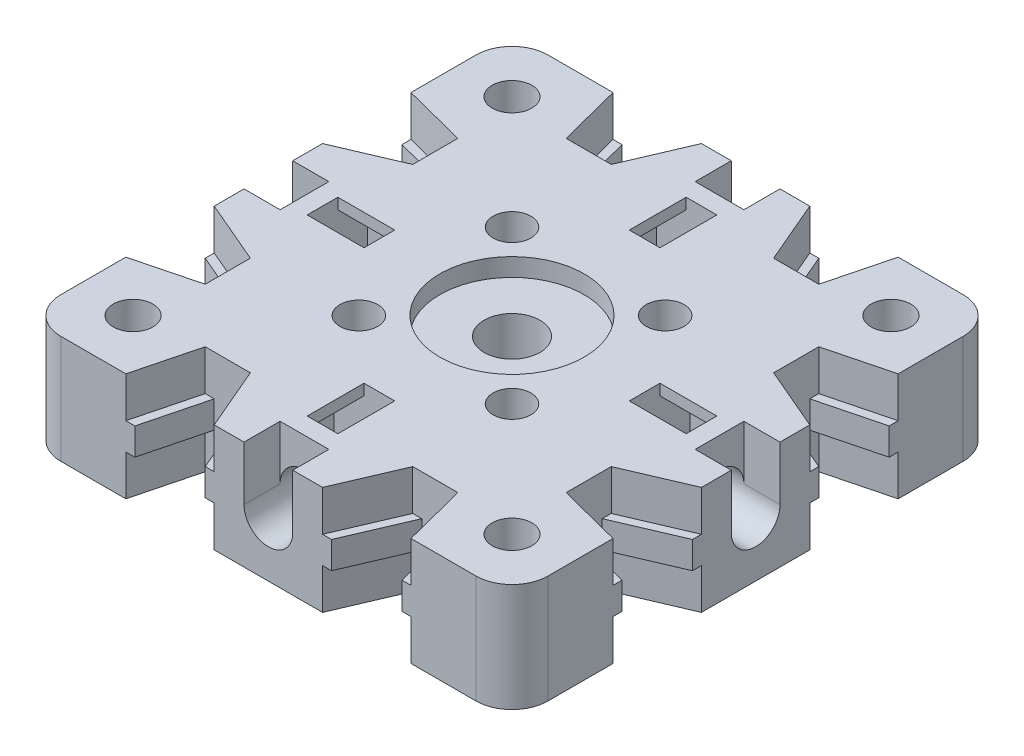
SolidWorks part; units mm, degrees
material "ABS"
ref_plane "正面" through (0, 0, 0) normal (0, 0, 1) x (1, 0, 0)
ref_plane "平面" through (0, 0, 0) normal (0, 1, 0) x (1, 0, 0)
ref_plane "右側面" through (0, 0, 0) normal (1, 0, 0) x (0, 0, -1)
sketch "ｽｹｯﾁ3" plane through (0, 0, 0) normal (0, 1, 0) x (1, 0, 0)
  line L1 (-13.5, 13.5) -> (13.5, 13.5)
  line L2 (-13.5, 13.5) -> (-13.5, -13.5)
  line L3 (-13.5, -13.5) -> (13.5, -13.5)
  line L4 (13.5, 13.5) -> (13.5, -13.5)
  line L5 (-13.5, 13.5) -> (13.5, -13.5) construction
  line L6 (-13.5, -13.5) -> (13.5, 13.5) construction
  point P0 (0, 0)
  dimension "D1" = 27
extrude "ﾎﾞｽ - 押し出し1" add sketch "ｽｹｯﾁ3" along normal mid plane 6
fillet "ﾌｨﾚｯﾄ1" radius 2 4 edges at (-13.5, 0, -13.5) (13.5, 0, -13.5) (-13.5, 0, 13.5) (13.5, 0, 13.5)
sketch "ｽｹｯﾁ4" plane through (0, 3, 0) normal (0, 1, 0) x (1, 0, 0)
  line L1 (-10.5, 10.5) -> (10.5, 10.5) construction
  line L2 (-10.5, 10.5) -> (-10.5, -10.5) construction
  line L3 (-10.5, -10.5) -> (10.5, -10.5) construction
  line L4 (10.5, 10.5) -> (10.5, -10.5) construction
  line L5 (-10.5, 10.5) -> (10.5, -10.5) construction
  line L6 (-10.5, -10.5) -> (10.5, 10.5) construction
  circle A0 centre (-10.5, 10.5) radius 1.1
  circle A1 centre (10.5, 10.5) radius 1.1
  circle A2 centre (-10.5, -10.5) radius 1.1
  circle A3 centre (10.5, -10.5) radius 1.1
  point P0 (0, 0)
  dimension "D6" = 2.2
  dimension "D1" = 21
  dimension "D2" = 21
extrude "ｶｯﾄ - 押し出し1" cut sketch "ｽｹｯﾁ4" against normal blind 6
sketch "ｽｹｯﾁ5" plane through (0, 3, 0) normal (0, 1, 0) x (1, 0, 0)
  circle A0 centre (0, 0) radius 1.55
  dimension "D1" = 3.1
extrude "ｶｯﾄ - 押し出し2" cut sketch "ｽｹｯﾁ5" against normal blind 6
sketch "ｽｹｯﾁ6" plane through (0, 3, 0) normal (0, 1, 0) x (1, 0, 0)
  line L0 (4.2426, 4.2426) -> (0, 0)
  line L1 (0, 0) -> (3.3762, 0)
  circle A0 centre (4.2426, 4.2426) radius 1.05
  dimension "D1" = 2.1
  dimension "D2" = 45
  dimension "D3" = 6
extrude "ｶｯﾄ - 押し出し3" cut sketch "ｽｹｯﾁ6" against normal blind 6
pattern_circular "円形ﾊﾟﾀｰﾝ1" count 4 over 360 about axis through (0, 0, 0) along (0, 1, 0) of "ｶｯﾄ - 押し出し3"
sketch "ｽｹｯﾁ7" plane through (0, 3, 0) normal (0, 1, 0) x (1, 0, 0)
  circle A0 centre (0, 0) radius 4
  dimension "D1" = 8
extrude "ｶｯﾄ - 押し出し4" cut sketch "ｽｹｯﾁ7" against normal blind 1
sketch "ｽｹｯﾁ8" plane through (0, -3, 0) normal (0, -1, 0) x (1, 0, 0)
  line L1 (-5.6, -5.6) -> (5.6, -5.6)
  line L2 (-5.6, -5.6) -> (-5.6, 5.6)
  line L3 (-5.6, 5.6) -> (5.6, 5.6)
  line L4 (5.6, -5.6) -> (5.6, 5.6)
  line L5 (-5.6, -5.6) -> (5.6, 5.6) construction
  line L6 (-5.6, 5.6) -> (5.6, -5.6) construction
  point P0 (0, 0)
  dimension "D1" = 11.2
extrude "ｶｯﾄ - 押し出し5" cut sketch "ｽｹｯﾁ8" against normal blind 2.5
sketch "ｽｹｯﾁ10" plane through (0, -3, 0) normal (0, -1, 0) x (1, 0, 0)
  circle A0 centre (4.2426, 4.2426) radius 2.35
  circle A1 centre (-4.2426, 4.2426) radius 2.35
  circle A2 centre (4.2426, -4.2426) radius 2.35
  circle A3 centre (-4.2426, -4.2426) radius 2.35
  dimension "D2" = 4.7
extrude "ｶｯﾄ - 押し出し7" [suppressed] cut sketch "ｽｹｯﾁ10" against normal blind 4
sketch "ｽｹｯﾁ11" plane through (0, 3, 0) normal (0, 1, 0) x (1, 0, 0)
  line L0 (3, 13.5) -> (4.5, 10)
  line L1 (11.5, 13.5) -> (-11.5, 13.5) construction
  line L2 (4.5, 10) -> (7, 10)
  line L3 (7, 10) -> (7.9, 13.5)
  dimension "D1" = 3.5
  dimension "D2" = 2.5
  dimension "D3" = 7
  dimension "D4" = 3
  dimension "D5" = 7.9
extrude "ｶｯﾄ - 押し出し8" cut sketch "ｽｹｯﾁ11" against normal through all and the other way through all
mirror "ﾐﾗｰ1" about plane through (0, 0, 0) normal (1, 0, 0) of "ｶｯﾄ - 押し出し8"
pattern_circular "円形ﾊﾟﾀｰﾝ2" count 4 over 360 about axis through (0, 0, 0) along (0, 1, 0) of "ｶｯﾄ - 押し出し8", "ﾐﾗｰ1"
sketch "ｽｹｯﾁ12" plane through (0, 0, 13.5) normal (0, 0, 1) x (1, 0, 0)
  circle A0 centre (0, 0) radius 1.35
  dimension "D1" = 2.7
extrude "ｶｯﾄ - 押し出し9" cut sketch "ｽｹｯﾁ12" against normal blind 8
pattern_circular "円形ﾊﾟﾀｰﾝ3" count 4 over 360 about axis through (0, 0, 0) along (0, 1, 0) of "ｶｯﾄ - 押し出し9"
sketch "ｽｹｯﾁ13" plane through (0, 0, 0) normal (0, 1, 0) x (1, 0, 0)
  line L0 (7.9, 13.5) -> (7, 10)
  line L1 (7, 10) -> (6.5, 10)
  line L2 (7, 10) -> (4.5, 10) construction
  line L3 (6.5, 10) -> (7.4, 13.5)
  line L4 (7.4, 13.5) -> (7.9, 13.5)
  line L5 (3, 13.5) -> (3.5, 13.5)
  line L6 (3.5, 13.5) -> (5, 10)
  line L7 (5, 10) -> (4.5, 10)
  line L8 (4.5, 10) -> (3, 13.5)
  dimension "D1" = 0.5
  dimension "D2" = 0.5
extrude "ﾎﾞｽ - 押し出し2" add sketch "ｽｹｯﾁ13" along normal mid plane 1.5
mirror "ﾐﾗｰ2" about plane through (0, 0, 0) normal (1, 0, 0) of "ﾎﾞｽ - 押し出し2"
pattern_circular "円形ﾊﾟﾀｰﾝ4" count 4 over 360 about axis through (0, 0, 0) along (0, 1, 0) of "ﾎﾞｽ - 押し出し2", "ﾐﾗｰ2"
ref_plane "平面1" through (0, 0, -10.5) normal (0, 0, -1) x (-1, 0, 0)
sketch "ｽｹｯﾁ14" plane through (0, 0, -10.5) normal (0, 0, -1) x (-1, 0, 0)
  line L1 (0, -2.8868) -> (2.5, -1.4434)
  line L2 (2.5, -1.4434) -> (2.5, 1.4434)
  line L3 (2.5, 1.4434) -> (0, 2.8868)
  line L4 (0, 2.8868) -> (-2.5, 1.4434)
  line L5 (-2.5, 1.4434) -> (-2.5, -1.4434)
  line L6 (-2.5, -1.4434) -> (0, -2.8868)
  line L7 (-3, 3) -> (-3, 0.75) construction
  line L8 (-2.5, -1.4434) -> (-2.5, -3)
  line L9 (-2.5, -3) -> (2.5, -3)
  line L10 (2.5, -3) -> (2.5, -1.4434)
  line L12 (-0.85, 3) -> (0.85, 3)
  line L13 (-0.85, 3) -> (-0.85, 0)
  line L14 (-0.85, 0) -> (0.85, 0)
  line L15 (0.85, 3) -> (0.85, 0)
  line L16 (-0.85, 3) -> (0.85, 0) construction
  line L17 (-0.85, 0) -> (0.85, 3) construction
  line L18 (-3, 3) -> (3, 3) construction
  circle A0 centre (0, 0) radius 2.5 construction
  circle A1 centre (0, 0) radius 1.35 construction
  point P19 (0, 1.5)
  dimension "D1" = 5
  dimension "D2" = 0
  dimension "D3" = 1.7
  dimension "D4" = 3
  dimension "D5" = 0
extrude "ｶｯﾄ - 押し出し10" cut sketch "ｽｹｯﾁ14" against normal blind 3.15 contours L3 L15 L14 L13 L4 L5 L6 L1 L2 | L15 L12 L13 L4 L3 | L15 L3 L4 L13 L14 | L9 L10 L1 L6 L8
sketch "ｽｹｯﾁ15" plane through (0, -3, 0) normal (0, -1, 0) x (1, 0, 0)
  line L0 (-1.254, -5.5) -> (1.254, -5.5) construction
  line L1 (-1.35, -5.5) -> (1.35, -5.5)
  line L2 (-1.35, -5.5) -> (-1.35, -7.35)
  line L3 (-1.35, -7.35) -> (1.35, -7.35)
  line L4 (1.35, -5.5) -> (1.35, -7.35)
  line L5 (-1.35, -5.5) -> (1.35, -7.35) construction
  line L6 (-1.35, -7.35) -> (1.35, -5.5) construction
  line L7 (2.5, -7.35) -> (-2.5, -7.35) construction
  point P4 (0, -6.425)
  dimension "D1" = 2.7
  dimension "D2" = 0
extrude "ｶｯﾄ - 押し出し11" cut sketch "ｽｹｯﾁ15" against normal blind 3
pattern_circular "円形ﾊﾟﾀｰﾝ5" count 4 over 360 about axis through (0, 0, 0) along (0, 1, 0) of "ｶｯﾄ - 押し出し10", "ｶｯﾄ - 押し出し11"
sketch "ｽｹｯﾁ16" plane through (0, -3, 0) normal (0, -1, 0) x (1, 0, 0)
  line L0 (-13.5, 7.9) -> (-13.5, 11.5) construction
  line L1 (-9.85, 8.0741) -> (-8.0741, 9.85)
  line L2 (-8.0741, 9.85) -> (-8.7241, 12.2759)
  line L3 (-8.7241, 12.2759) -> (-11.15, 12.9259)
  line L4 (-11.15, 12.9259) -> (-12.9259, 11.15)
  line L5 (-12.9259, 11.15) -> (-12.2759, 8.7241)
  line L6 (-12.2759, 8.7241) -> (-9.85, 8.0741)
  circle A0 centre (-10.5, 10.5) radius 2.175 construction
  point P11 (-8.3991, 11.0629)
  dimension "D1" = 15
  dimension "D2" = 4.35
extrude "ｶｯﾄ - 押し出し12" cut sketch "ｽｹｯﾁ16" against normal blind 4.1
sketch "ｽｹｯﾁ17" plane through (0, -3, 0) normal (0, -1, 0) x (1, 0, 0)
  line L0 (0.8839, 0.8839) -> (-8.8383, 10.6061)
  line L1 (0.8839, 0.8839) -> (-0.8839, -0.8839)
  line L2 (-8.8383, 10.6061) -> (-10.6061, 8.8383)
  line L3 (-0.8839, -0.8839) -> (-10.6061, 8.8383)
  line L4 (0.8839, 0.8839) -> (-10.6061, 8.8383) construction
  line L5 (-8.8383, 10.6061) -> (-0.8839, -0.8839) construction
  circle A0 centre (-10.5, 10.5) radius 1.1 construction
  point P1 (-4.8611, 4.8611)
  dimension "D1" = 2.5
  dimension "D2" = 1.25
extrude "ｶｯﾄ - 押し出し13" cut sketch "ｽｹｯﾁ17" against normal blind 1
pattern_circular "円形ﾊﾟﾀｰﾝ6" count 4 over 360 about axis through (0, 0, 0) along (0, 1, 0) of "ｶｯﾄ - 押し出し12", "ｶｯﾄ - 押し出し13"
sketch "ｽｹｯﾁ18" plane through (0, 3, 0) normal (0, 1, 0) x (1, 0, 0)
  line L0 (0, 0) -> (6, 0)
  line L1 (0, 0) -> (0, 6)
  dimension "D1" = 6
sketch "ｽｹｯﾁ19" plane through (0, 0, 0) normal (0, 0, 1) x (1, 0, 0)
  line L0 (0, 3) -> (0, 9)
  line L1 (0, 3) -> (6, 3) construction
sketch "ｽｹｯﾁ21" plane through (0, -3, 0) normal (0, -1, 0) x (1, 0, 0)
  line L1 (-3.6375, 1.984) -> (-1.984, 3.6375)
  line L2 (-1.984, 3.6375) -> (-2.5892, 5.896)
  line L3 (-2.5892, 5.896) -> (-4.8478, 6.5012)
  line L4 (-4.8478, 6.5012) -> (-6.5012, 4.8478)
  line L5 (-6.5012, 4.8478) -> (-5.896, 2.5892)
  line L6 (-5.896, 2.5892) -> (-3.6375, 1.984)
  line L8 (-9.8459, 8.0782) -> (-8.0782, 9.8459) construction
  circle A0 centre (-4.2426, 4.2426) radius 2.025 construction
  point P11 (-2.8107, 2.8107)
  dimension "D1" = 4.05
extrude "ｶｯﾄ - 押し出し14" cut sketch "ｽｹｯﾁ21" against normal blind 3.8
pattern_circular "円形ﾊﾟﾀｰﾝ7" count 4 over 360 about axis through (0, 0, 0) along (0, 1, 0) of "ｶｯﾄ - 押し出し14"
sketch "ｽｹｯﾁ22" plane through (0, 0, 13.5) normal (0, 0, 1) x (1, 0, 0)
  line L0 (0, 3) -> (6, 3) construction
  line L1 (-1.35, 0) -> (1.35, 0)
  line L2 (-1.35, 0) -> (-1.35, 3)
  line L3 (-1.35, 3) -> (1.35, 3)
  line L4 (1.35, 0) -> (1.35, 3)
  line L5 (-1.35, 0) -> (1.35, 3) construction
  line L6 (-1.35, 3) -> (1.35, 0) construction
  arc A0 (1.35, 0) -> (-1.35, 0) centre (0, 0) ccw construction
  circle A1 centre (0, 0) radius 1.35 construction
  point P4 (0, 1.5)
extrude "ｶｯﾄ - 押し出し15" cut sketch "ｽｹｯﾁ22" against normal blind 2
sketch "ｽｹｯﾁ23" plane through (0, -3, 0) normal (0, -1, 0) x (1, 0, 0)
  line L1 (-8, 8) -> (-4.4, 8)
  line L2 (-8, 8) -> (-8, 4.4)
  line L3 (-8, 4.4) -> (-4.4, 4.4)
  line L4 (-4.4, 8) -> (-4.4, 4.4)
  line L5 (-8, 8) -> (-4.4, 4.4) construction
  line L6 (-8, 4.4) -> (-4.4, 8) construction
  circle A0 centre (-4.2426, 4.2426) radius 2.9
  point P8 (-6.2, 6.2)
  dimension "D1" = 5.8
  dimension "D2" = 8
  dimension "D3" = 8
  dimension "D4" = 4.4
extrude "ｶｯﾄ - 押し出し16" cut sketch "ｽｹｯﾁ23" against normal blind 3.5 contours A0 L4 L1 L2 L3
pattern_circular "円形ﾊﾟﾀｰﾝ8" count 4 over 360 about axis through (0, 0, 0) along (0, 1, 0) of "ｶｯﾄ - 押し出し16"
fillet "ﾌｨﾚｯﾄ2" radius 0.3 20 edges at (-4.4, -1.25, -7.1384) (-4.4, -1.25, -8) (-8, -0.75, -8) (-7.1384, -1.25, -4.4) (-8, -1.25, -4.4) (8, -0.75, -8) (4.4, -1.25, -8) (4.4, -1.25, -7.1384) (8, -1.25, -4.4) (7.1384, -1.25, -4.4) (7.1384, -1.25, 4.4) (8, -1.25, 4.4) (8, -0.75, 8) (4.4, -1.25, 7.1384) (4.4, -1.25, 8) (-4.4, -1.25, 7.1384) (-7.1384, -1.25, 4.4) (-8, -1.25, 4.4) (-8, -0.75, 8) (-4.4, -1.25, 8)
sketch "ｽｹｯﾁ25" plane through (0, -3, 0) normal (0, -1, 0) x (1, 0, 0)
  line L3 (-7.4098, 4.4) -> (-4.4, 4.4)
  line L4 (-4.4, 4.4) -> (-4.4, 7.4098)
  line L5 (-4.4, 7.4098) -> (-7.4098, 7.4098)
  line L6 (-7.4098, 7.4098) -> (-7.4098, 4.4)
extrude "ｶｯﾄ - 押し出し17" cut sketch "ｽｹｯﾁ25" against normal up to surface (2.5 mm away) up to face at (0, -0.5, 0)
pattern_circular "円形ﾊﾟﾀｰﾝ10" count 4 over 360 about axis through (0, 0, 0) along (0, 1, 0) of "ｶｯﾄ - 押し出し17"
fillet "ﾌｨﾚｯﾄ3" radius 0.3 8 edges at (-4.4, -1.75, 6.3812) (-6.3812, -1.75, 4.4) (6.3812, -1.75, 4.4) (4.4, -1.75, 6.3812) (4.4, -1.75, -6.3812) (6.3812, -1.75, -4.4) (-4.4, -1.75, -6.3812) (-6.3812, -1.75, -4.4)
pattern_circular "円形ﾊﾟﾀｰﾝ11" count 4 over 360 about axis through (0, 0, 0) along (0, 1, 0) of "ｶｯﾄ - 押し出し15"
sketch "ｽｹｯﾁ27" plane through (0, -3, 0) normal (0, -1, 0) x (1, 0, 0)
  line L0 (0, -6) -> (0, 0)
  line L1 (0, 0) -> (-6, 0)
